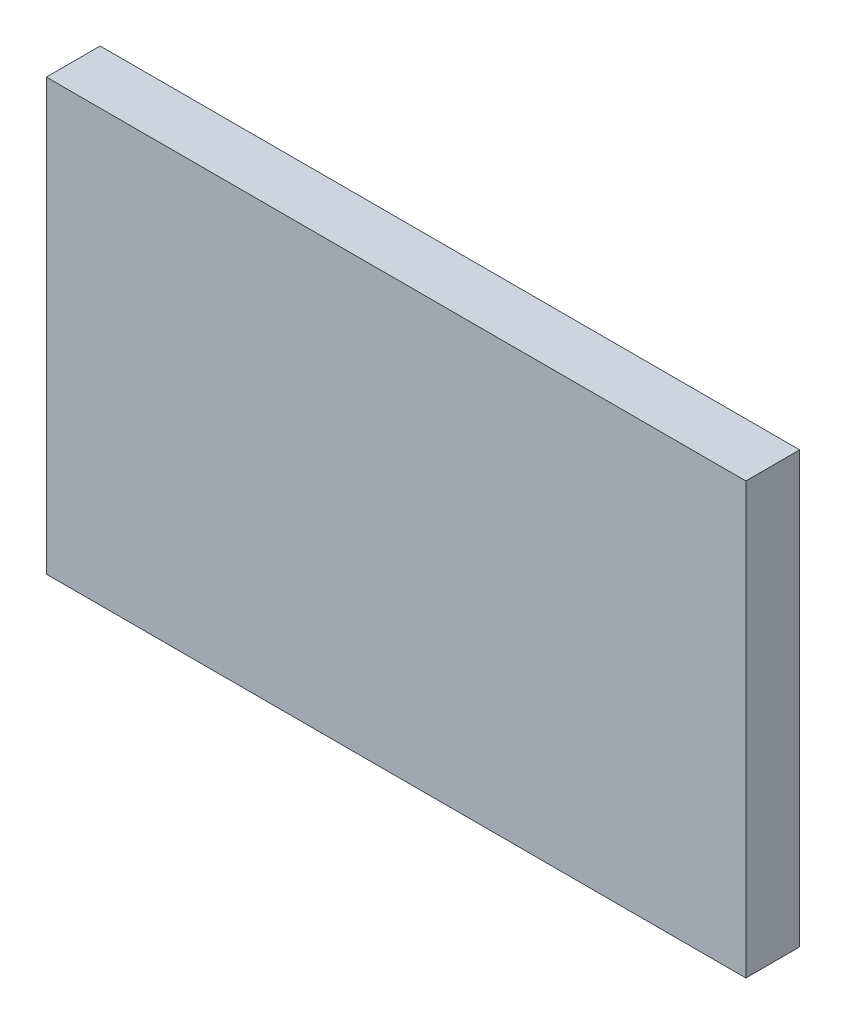
SolidWorks part; units mm, degrees
ref_plane "Front Plane" through (0, 0, 0) normal (0, 0, 1) x (1, 0, 0)
ref_plane "Top Plane" through (0, 0, 0) normal (0, 1, 0) x (1, 0, 0)
ref_plane "Right Plane" through (0, 0, 0) normal (1, 0, 0) x (0, 0, -1)
sketch "Sketch1" plane through (0, 0, 0) normal (0, 0, 1) x (1, 0, 0)
  line L1 (-7.5, 10) -> (7.5, 10)
  line L2 (-7.5, 10) -> (-7.5, -10)
  line L3 (-7.5, -10) -> (7.5, -10)
  line L4 (7.5, 10) -> (7.5, -10)
  line L5 (-7.5, 10) -> (7.5, -10) construction
  line L6 (-7.5, -10) -> (7.5, 10) construction
  point P0 (0, 0)
  dimension "D1" = 15
  dimension "D2" = 20
extrude "Boss-Extrude1" add sketch "Sketch1" along normal blind 230
sketch "Sketch2" plane through (0, 0, 0) normal (0, 0, -1) x (-1, 0, 0)
  line L1 (-32.5, 10) -> (32.5, 10)
  line L2 (-32.5, 10) -> (-32.5, 50)
  line L3 (-32.5, 50) -> (32.5, 50)
  line L4 (32.5, 10) -> (32.5, 50)
  line L6 (-7.5, 10) -> (7.5, 10) construction
  point P4 (0, 10)
  point P10 (0, 10)
  dimension "D1" = 65
  dimension "D2" = 40
extrude "Boss-Extrude6" add sketch "Sketch2" against normal blind 5 separate body
sketch "Sketch7" plane through (32.5, 0, 0) normal (1, 0, 0) x (0, 0, -1)
  line L0 (0, 50) -> (0, 10) construction
  line L1 (0, 37.5) -> (-75, 37.5)
  line L2 (0, 37.5) -> (0, 22.5)
  line L3 (0, 22.5) -> (-75, 22.5)
  line L4 (-75, 37.5) -> (-75, 22.5)
  point P4 (0, 30)
  point P7 (0, 30)
  dimension "D1" = 15
  dimension "D2" = 75
extrude "Boss-Extrude7" add sketch "Sketch7" along normal blind 5 separate body
sketch "Sketch8" plane through (-32.5, 0, 0) normal (-1, 0, 0) x (0, 0, 1)
  line L1 (0, 37.5) -> (75, 37.5)
  line L2 (0, 37.5) -> (0, 22.5)
  line L3 (0, 22.5) -> (75, 22.5)
  line L4 (75, 37.5) -> (75, 22.5)
extrude "Boss-Extrude8" add sketch "Sketch8" along normal blind 5 separate body
sketch "Sketch9" plane through (0, 0, 75) normal (0, 0, 1) x (1, 0, 0)
  line L1 (-32.5, 50) -> (32.5, 50)
  line L2 (-32.5, 50) -> (-32.5, 10)
  line L3 (-32.5, 10) -> (32.5, 10)
  line L4 (32.5, 50) -> (32.5, 10)
extrude "Boss-Extrude11" add sketch "Sketch9" against normal blind 5 separate body
sketch "Sketch10" plane through (-7.5, 0, 0) normal (-1, 0, 0) x (0, 0, 1)
  line L0 (230, 10) -> (230, -10) construction
  line L2 (209.8431, 2) -> (211.3431, 2)
  line L3 (209.8431, 2) -> (209.8431, -2)
  line L4 (209.8431, -2) -> (211.3431, -2)
  line L6 (209.8431, 2) -> (211, 0) construction
  line L7 (209.8431, -2) -> (211, 0) construction
  arc A0 (211.3431, -2) -> (211.3431, 2) centre (217, 0) ccw
  point P4 (230, 0)
  point P5 (211, 0)
  point P11 (209.8431, 0)
  dimension "D1" = 12
  dimension "D2" = 13
  dimension "D3" = 1.5
  dimension "D4" = 4
extrude "Cut-Extrude1" cut sketch "Sketch10" against normal through all
delete or keep bodies "Body-Delete/Keep 3" type delete bodies bodies 106 107 108 110
